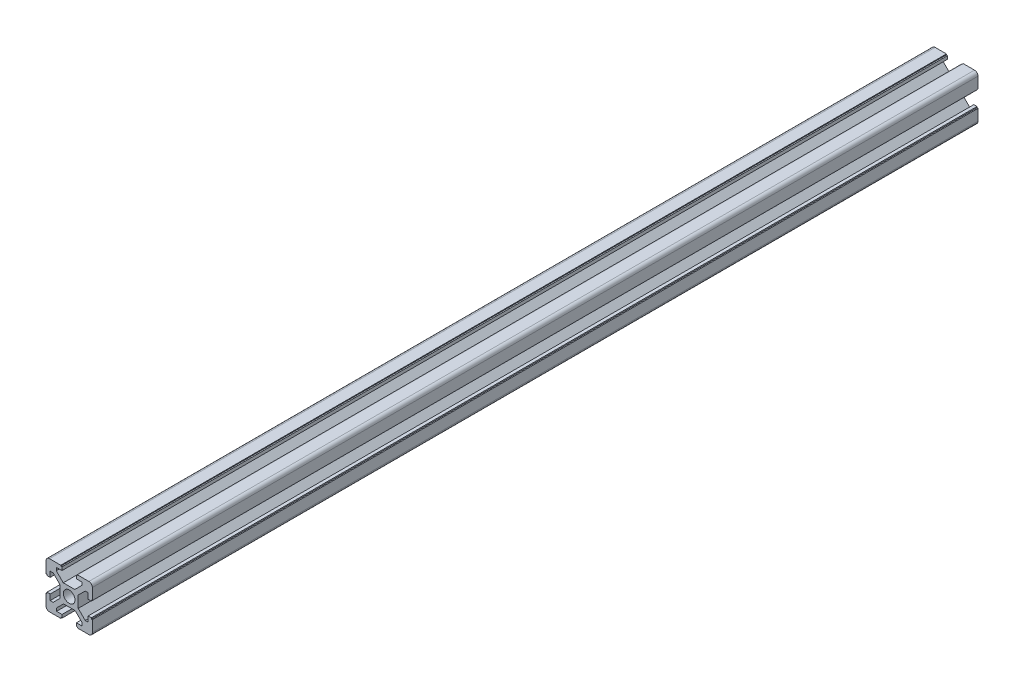
SolidWorks part; units mm, degrees
ref_plane "Front Plane" through (0, 0, 0) normal (0, 0, 1) x (1, 0, 0)
ref_plane "Top Plane" through (0, 0, 0) normal (0, 1, 0) x (1, 0, 0)
ref_plane "Right Plane" through (0, 0, 0) normal (1, 0, 0) x (0, 0, -1)
sketch "Sketch1" plane through (0, 0, 0) normal (0, 0, 1) x (1, 0, 0)
  line L0 (240.9169, 601.7923) -> (1204.5843, 601.7923) construction
  line L6 (13.0291, 10.3872) -> (13.0291, 12.8554)
  line L7 (12.7291, 6.0212) -> (29.7291, 6.0212)
  line L11 (11.2291, 7.5212) -> (11.2291, 24.3895)
  line L12 (12.7291, 25.8895) -> (29.7291, 25.8895)
  line L13 (31.2291, 7.5212) -> (31.2291, 24.3895)
  line L14 (11.2291, 6.0212) -> (31.2291, 25.8895) construction
  line L15 (11.2291, 25.8895) -> (31.2291, 6.0212) construction
  line L16 (13.0291, 24.0895) -> (13.041, 24.0895)
  line L17 (29.4291, 10.5205) -> (29.4291, 12.8554)
  line L18 (13.0291, 7.8212) -> (13.041, 7.8212)
  line L19 (11.2291, 15.9554) -> (31.2291, 15.9554) construction
  line L20 (11.6567, 12.8554) -> (13.0291, 12.8554)
  line L21 (11.6567, 19.0554) -> (13.0291, 19.0554)
  line L22 (21.2291, 6.0212) -> (21.2291, 25.8895) construction
  line L23 (24.8338, 25.9554) -> (24.8338, 25.5277)
  line L24 (17.3291, 21.0535) -> (17.3291, 19.8297)
  line L25 (11.2291, 19.56) -> (11.6567, 19.56)
  line L26 (11.6567, 19.56) -> (11.6567, 19.0554)
  line L27 (11.6567, 19.0554) -> (13.0291, 19.0554)
  line L28 (17.3291, 18.3778) -> (14.3166, 21.3903)
  line L29 (14.3166, 21.3903) -> (13.0291, 21.3903)
  line L30 (17.3291, 13.3997) -> (14.3166, 10.3872)
  line L31 (14.3166, 10.3872) -> (13.0291, 10.3872)
  line L32 (13.0291, 7.8212) -> (13.0291, 24.0895) construction
  line L33 (29.4172, 7.8212) -> (29.4291, 7.8212)
  line L34 (13.0291, 7.8212) -> (29.4291, 7.8212) construction
  line L35 (17.3291, 12.081) -> (17.3291, 10.641)
  line L36 (24.8338, 25.5277) -> (24.3291, 25.5277)
  line L37 (11.2291, 12.8554) -> (31.2291, 12.8554) construction
  line L38 (24.3291, 25.5277) -> (24.3291, 24.1554)
  line L39 (11.2291, 19.0554) -> (31.2291, 19.0554) construction
  line L40 (17.3291, 18.3778) -> (17.3291, 13.3997)
  line L41 (11.6567, 12.8554) -> (11.6567, 12.3367)
  line L42 (11.6567, 12.3367) -> (11.2291, 12.3367)
  line L43 (13.0291, 19.0554) -> (13.0291, 21.3903)
  line L44 (24.3291, 24.1554) -> (26.664, 24.1554)
  line L45 (26.664, 22.8679) -> (26.664, 24.1554)
  line L46 (23.6515, 19.8554) -> (26.664, 22.8679)
  line L47 (23.6515, 19.8554) -> (18.6734, 19.8554)
  line L48 (18.6734, 19.8554) -> (15.661, 22.8679)
  line L49 (15.661, 24.1554) -> (18.1291, 24.1554)
  line L50 (15.661, 22.8679) -> (15.661, 24.1554)
  line L51 (18.1291, 25.5277) -> (18.1291, 24.1554)
  line L52 (18.1291, 25.5277) -> (17.6104, 25.5277)
  line L53 (17.6104, 25.5277) -> (17.6104, 25.9554)
  line L54 (31.2291, 12.3507) -> (30.8015, 12.3507)
  line L55 (30.8015, 12.3507) -> (30.8015, 12.8554)
  line L56 (30.8015, 12.8554) -> (29.4291, 12.8554)
  line L57 (29.4291, 12.8554) -> (29.4291, 10.5205)
  line L58 (28.1416, 10.5205) -> (29.4291, 10.5205)
  line L59 (25.1291, 13.533) -> (28.1416, 10.5205)
  line L60 (25.1291, 13.533) -> (25.1291, 18.511)
  line L61 (25.1291, 18.511) -> (28.1416, 21.5235)
  line L62 (29.4291, 21.5235) -> (29.4291, 19.0554)
  line L63 (28.1416, 21.5235) -> (29.4291, 21.5235)
  line L64 (30.8015, 19.0554) -> (29.4291, 19.0554)
  line L65 (30.8015, 19.0554) -> (30.8015, 19.5741)
  line L66 (30.8015, 19.5741) -> (31.2291, 19.5741)
  line L67 (17.6244, 5.9554) -> (17.6244, 6.383)
  line L68 (17.6244, 6.383) -> (18.1291, 6.383)
  line L69 (18.1291, 6.383) -> (18.1291, 7.7554)
  line L70 (18.1291, 7.7554) -> (15.7942, 7.7554)
  line L71 (15.7942, 9.0429) -> (15.7942, 7.7554)
  line L72 (18.8067, 12.0554) -> (15.7942, 9.0429)
  line L73 (18.8067, 12.0554) -> (23.7848, 12.0554)
  line L74 (23.7848, 12.0554) -> (26.7973, 9.0429)
  line L75 (26.7973, 7.7554) -> (24.3291, 7.7554)
  line L76 (26.7973, 9.0429) -> (26.7973, 7.7554)
  line L77 (24.3291, 6.383) -> (24.3291, 7.7554)
  line L78 (24.3291, 6.383) -> (24.8478, 6.383)
  line L79 (24.8478, 6.383) -> (24.8478, 5.9554)
  line L80 (29.4172, 24.0895) -> (29.4291, 24.0895)
  line L81 (13.0291, 24.0895) -> (29.4291, 24.0895) construction
  line L82 (29.4291, 19.0554) -> (29.4291, 21.5235)
  line L83 (29.4291, 7.8212) -> (29.4291, 24.0895) construction
  circle A1 centre (21.2291, 15.9554) radius 2.5
  arc A2 (12.7291, 25.8895) -> (11.2291, 24.3895) centre (12.7291, 24.3895) ccw
  arc A3 (11.2291, 7.5212) -> (12.7291, 6.0212) centre (12.7291, 7.5212) ccw
  arc A4 (29.7291, 6.0212) -> (31.2291, 7.5212) centre (29.7291, 7.5212) ccw
  arc A5 (31.2291, 24.3895) -> (29.7291, 25.8895) centre (29.7291, 24.3895) ccw
  arc A6 (13.0291, 24.0895) -> (13.0291, 24.0895) centre (13.0291, 24.0895) ccw
  arc A7 (29.4291, 24.0895) -> (29.4291, 24.0895) centre (29.4291, 24.0895) ccw
  arc A8 (29.4291, 7.8212) -> (29.4291, 7.8212) centre (29.4291, 7.8212) ccw
  arc A9 (13.0291, 7.8212) -> (13.0291, 7.8212) centre (13.0291, 7.8212) ccw
  point P105 (21.2291, 15.9554)
  dimension "D1" = 20
  dimension "D2" = 1.5
  dimension "D3" = 1.5
  dimension "D7" = 4
  dimension "D8" = 6.1
  dimension "D4" = 1.8
  dimension "D5" = 3.1
  dimension "D6" = 3.1
extrude "Boss-Extrude1" add sketch "Sketch1" along normal blind 382 contours L13 A5 L12 L23 L36 L38 L44 L45 L46 L47 L48 L50 L49 L51 L52 L53 A2 L11 L25 L26 L21 L43 L29 L28 L40 L30 L31 L6 L20 L41 L42 region at (13.6729, 10.1053, 0)
